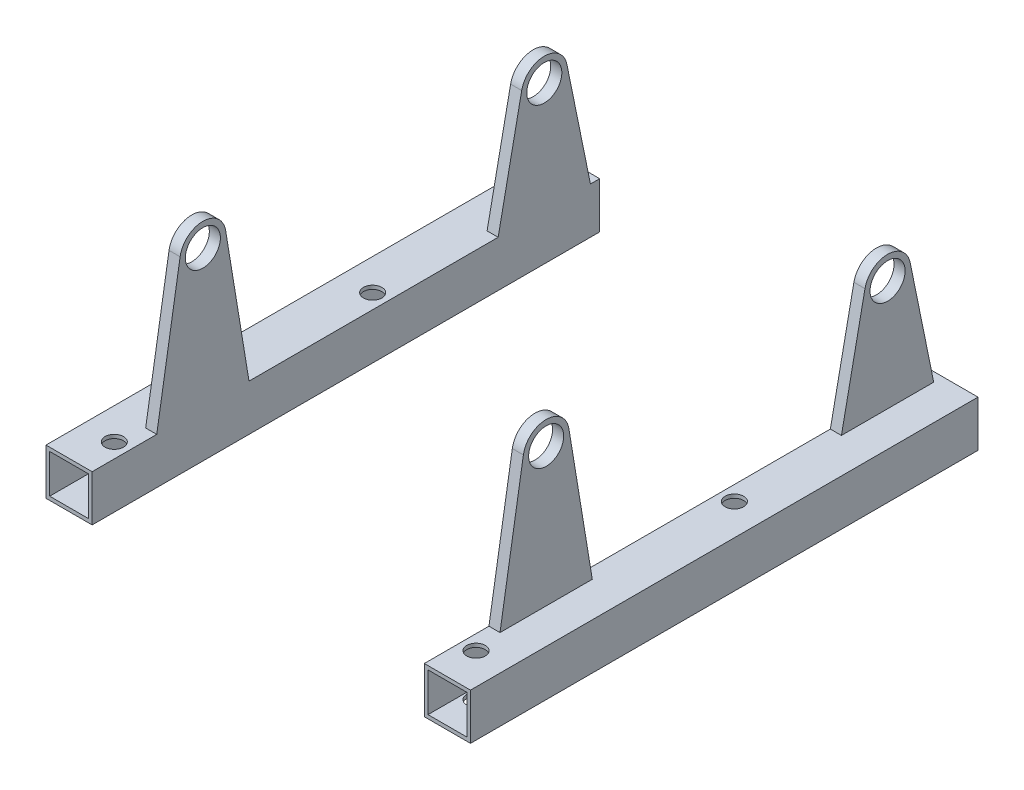
SolidWorks part; units mm, degrees
ref_plane "Front Plane" through (0, 0, 0) normal (0, 0, 1) x (1, 0, 0)
ref_plane "Top Plane" through (0, 0, 0) normal (0, 1, 0) x (1, 0, 0)
ref_plane "Right Plane" through (0, 0, 0) normal (1, 0, 0) x (0, 0, -1)
sketch "Sketch1" plane through (0, 0, 0) normal (0, 1, 0) x (1, 0, 0)
  line L0 (-115, -155) -> (-115, 155)
  line L1 (-90, -130) -> (90, -130)
  line L2 (-90, -130) -> (-90, 130)
  line L4 (90, -130) -> (90, 130)
  line L5 (-90, -130) -> (90, 130) construction
  line L6 (-90, 130) -> (90, -130) construction
  line L7 (-115, 155) -> (-90, 155)
  line L8 (115, -155) -> (115, 155)
  line L9 (-115, -155) -> (115, -155)
  line L10 (-90, 130) -> (-90, 155)
  line L11 (90, 130) -> (90, 155)
  line L12 (90, 155) -> (115, 155)
  line L13 (-90, 130) -> (90, 130) construction
  line L15 (-115, 155) -> (115, 155) construction
  point P0 (0, 0)
  dimension "D1" = 180
  dimension "D2" = 260
  dimension "D3" = 25
extrude "Boss-Extrude1" add sketch "Sketch1" along normal mid plane 25
shell "Shell1" thickness 2
sketch "Sketch6" plane through (-90, 0, 0) normal (1, 0, 0) x (0, 0, -1)
  line L0 (-155, 12.5) -> (155, 12.5) construction
  line L1 (-155, 12.5) -> (-155, -12.5) construction
  line L2 (-107.3344, 89.5281) -> (-120, 12.5)
  line L3 (-130, 12.5) -> (155, 12.5) construction
  line L4 (-82.6656, 89.5281) -> (-70, 12.5)
  line L5 (-120, 12.5) -> (-70, 12.5)
  line L6 (-95, 87.5) -> (-95, 40.2407) construction
  arc A0 (-82.6656, 89.5281) -> (-107.3344, 89.5281) centre (-95, 87.5) ccw
  circle A1 centre (-95, 87.5) radius 9.5
  dimension "D5" = 25
  dimension "D6" = 19
  dimension "D1" = 75
  dimension "D2" = 60
  dimension "D3" = 50
extrude "Boss-Extrude5" add sketch "Sketch6" against normal blind 6
pattern_linear "LPattern1" count 2 spacing 186 along (1, 0, 0) of "Boss-Extrude5"
sketch "Sketch9" plane through (90, 0, 0) normal (-1, 0, 0) x (0, 0, 1)
  line L0 (-90, 72.5) -> (-90, 33.7376) construction
  line L1 (-155, 12.5) -> (155, 12.5) construction
  line L2 (-77.7524, 74.999) -> (-65, 12.5)
  line L3 (-65, 12.5) -> (-115, 12.5)
  line L4 (-115, 12.5) -> (-102.2476, 74.999)
  circle A0 centre (-90, 72.5) radius 9.5
  arc A1 (-77.7524, 74.999) -> (-102.2476, 74.999) centre (-90, 72.5) ccw
  circle A3 centre (95, 87.5) radius 9.5 construction
  dimension "D3" = 25
  dimension "D4" = 19
  dimension "D1" = 185
  dimension "D2" = 60
  dimension "D5" = 50
extrude "Boss-Extrude6" add sketch "Sketch9" against normal blind 6
ref_plane "Plane1" through (0, 0, 0) normal (1, 0, 0) x (0, 0, -1)
mirror "Mirror1" about plane through (0, 0, 0) normal (1, 0, 0) of "Boss-Extrude6"
sketch "Sketch10" plane through (0, 12.5, 0) normal (0, 1, 0) x (1, 0, 0)
  line L0 (-115, -155) -> (115, -155) construction
  line L1 (-90, -130) -> (90, -130)
  line L2 (-90, -130) -> (-90, -155)
  line L3 (-90, -155) -> (90, -155)
  line L4 (90, -130) -> (90, -155)
extrude "Cut-Extrude1" cut sketch "Sketch10" against normal through all
sketch "Sketch11" plane through (0, 12.5, 0) normal (0, 1, 0) x (1, 0, 0)
  line L1 (0, 0) -> (0, 29.6777) construction
  line L2 (-115, -155) -> (-90, -155) construction
  line L3 (-115, 155) -> (-115, -155) construction
  circle A0 centre (-98, 5) radius 5
  circle A1 centre (-98, -135) radius 5
  circle A2 centre (98, -135) radius 5
  circle A3 centre (98, 5) radius 5
  dimension "D1" = 10
  dimension "D2" = 10
  dimension "D3" = 20
  dimension "D4" = 140
  dimension "D5" = 17
extrude "Cut-Extrude2" cut sketch "Sketch11" against normal through all
sketch "Sketch12" plane through (0, 12.5, 0) normal (0, 1, 0) x (1, 0, 0)
  line L0 (115, -155) -> (115, 155) construction
  line L1 (-115, 155) -> (115, 155)
  line L2 (-115, 155) -> (-115, 120)
  line L3 (-115, 120) -> (115, 120)
  line L4 (115, 155) -> (115, 120)
  dimension "D1" = 35
extrude "Cut-Extrude3" cut sketch "Sketch12" against normal through all
sketch "Sketch13" plane through (92, 0, 0) normal (1, 0, 0) x (0, 0, -1)
  line L1 (-132, 10.5) -> (-153, 10.5)
  line L2 (-132, 10.5) -> (-132, -10.5)
  line L3 (-132, -10.5) -> (-153, -10.5)
  line L4 (-153, 10.5) -> (-153, -10.5)
extrude "Boss-Extrude7" add sketch "Sketch13" against normal up to surface (2 mm away) up to face at (90, 33.2939, 7.5)
sketch "Sketch14" plane through (-92, 0, 0) normal (-1, 0, 0) x (0, 0, 1)
  line L1 (132, -10.5) -> (153, -10.5)
  line L2 (132, -10.5) -> (132, 10.5)
  line L3 (132, 10.5) -> (153, 10.5)
  line L4 (153, -10.5) -> (153, 10.5)
extrude "Boss-Extrude8" add sketch "Sketch14" against normal up to surface (2 mm away) up to face at (-90, 33.2939, 7.5)
sketch "Sketch16" plane through (0, 0, -120) normal (0, 0, -1) x (-1, 0, 0)
  line L1 (-113, 10.5) -> (-92, 10.5)
  line L2 (-113, 10.5) -> (-113, -10.5)
  line L3 (-113, -10.5) -> (-92, -10.5)
  line L4 (-92, 10.5) -> (-92, -10.5)
  line L5 (92, 10.5) -> (113, 10.5)
  line L6 (92, 10.5) -> (92, -10.5)
  line L7 (92, -10.5) -> (113, -10.5)
  line L8 (113, 10.5) -> (113, -10.5)
extrude "Cut-Extrude5" cut sketch "Sketch16" against normal up to surface (275 mm away) up to face at (-102.5, 0, 155)
